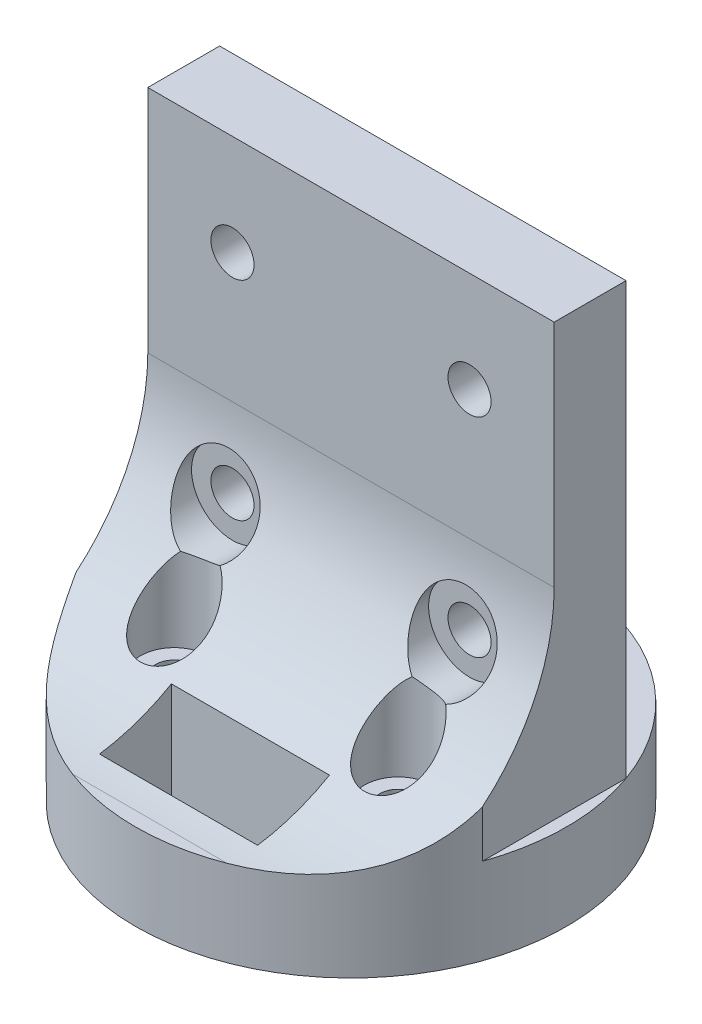
SolidWorks part; units mm, degrees
material "PVC 0.007 塑化"
ref_plane "前视基准面" through (0, 0, 0) normal (0, 0, 1) x (1, 0, 0)
ref_plane "上视基准面" through (0, 0, 0) normal (0, 1, 0) x (1, 0, 0)
ref_plane "右视基准面" through (0, 0, 0) normal (1, 0, 0) x (0, 0, -1)
sketch "草图1" plane through (0, 0, 0) normal (0, 1, 0) x (1, 0, 0)
  line L0 (0, 0) -> (0, 29.3447) construction
  line L1 (0, 0) -> (0, 9) construction
  line L2 (0, 0) -> (0, -24.464) construction
  line L4 (-5.5, -7) -> (5.5, -7)
  line L5 (-5.5, -7) -> (-5.5, -12)
  line L6 (-5.5, -12) -> (5.5, -12)
  line L7 (5.5, -7) -> (5.5, -12)
  circle A0 centre (0, 0) radius 15
  circle A1 centre (0, 0) radius 9 construction
  circle A2 centre (0, 9) radius 1.3
  circle A3 centre (7.7942, -4.5) radius 1.3
  circle A4 centre (-7.7942, -4.5) radius 1.3
  dimension "D1" = 30
  dimension "D2" = 18
  dimension "D3" = 2.6
  dimension "D6" = 11
  dimension "D7" = 5
  dimension "D8" = 7
  dimension "D4" = 3
extrude "凸台-拉伸1" add sketch "草图1" along normal blind 6
sketch "草图2" plane through (0, 6, 0) normal (0, 1, 0) x (1, 0, 0)
  line L0 (0, 2.5) -> (12.2513, 2.5) construction
  line L2 (-14.1421, 5) -> (14.1421, 5)
  line L3 (-14.1421, 5) -> (-14.1421, 0)
  line L4 (-14.1421, 0) -> (14.1421, 0)
  line L5 (14.1421, 5) -> (14.1421, 0)
  line L6 (-14.1421, 5) -> (14.1421, 0) construction
  line L7 (-14.1421, 0) -> (14.1421, 5) construction
  circle A2 centre (0, 0) radius 15 construction
  dimension "D1" = 5
extrude "凸台-拉伸2" add sketch "草图2" along normal blind 30
sketch "草图3" plane through (0, 0, -5) normal (0, 0, -1) x (-1, 0, 0)
  line L0 (-14.1421, 6) -> (14.1421, 6) construction
  line L3 (0, 21) -> (0, 39.3535) construction
  line L4 (-14.1421, 36) -> (-14.1421, 6) construction
  line L5 (14.1421, 36) -> (14.1421, 6) construction
  line L11 (14.1421, 6) -> (-14.1421, 6) construction
  line L12 (-18.8365, 21.75) -> (-3.6637, 21.75) construction
  circle A0 centre (-8.25, 14.5) radius 1.5
  circle A1 centre (8.25, 14.5) radius 1.5
  circle A2 centre (8.25, 29) radius 1.5
  circle A3 centre (-8.25, 29) radius 1.5
  point P1 (0, 0)
  dimension "D4" = 3
  dimension "D6" = 19.5
  dimension "D1" = 7
  dimension "D2" = 24.5
extrude "切除-拉伸1" cut sketch "草图3" against normal through all and the other way through all
fillet "圆角2" radius 14 1 edges at (0, 6, 0)
sketch "草图4" plane through (0, 6, 0) normal (0, 1, 0) x (1, 0, 0)
  circle A0 centre (0, 9) radius 2.35
  circle A1 centre (7.7942, -4.5) radius 2.35
  circle A2 centre (-7.7942, -4.5) radius 2.35
  dimension "D1" = 4.7
  dimension "D2" = 4.7
  dimension "D3" = 4.7
extrude "切除-拉伸2" cut sketch "草图4" along normal through all
sketch "草图5" plane through (0, 0, 0) normal (0, 0, 1) x (1, 0, 0)
  circle A0 centre (8.25, 14.5) radius 2.85
  circle A1 centre (-8.25, 14.5) radius 2.85
  dimension "D1" = 5.7
  dimension "D2" = 5.7
extrude "切除-拉伸3" cut sketch "草图5" along normal through all
sketch "草图6" plane through (0, 0, -5) normal (0, 0, -1) x (-1, 0, 0)
  line L5 (-14.1421, 36) -> (14.1421, 36) construction
  line L6 (-14.1421, 36) -> (-14.1421, 6) construction
  circle A0 centre (-12.1421, 34) radius 0.75
  dimension "D1" = 1.5
  dimension "D2" = 2
  dimension "D3" = 2
extrude "切除-拉伸4" cut sketch "草图6" against normal blind 1
